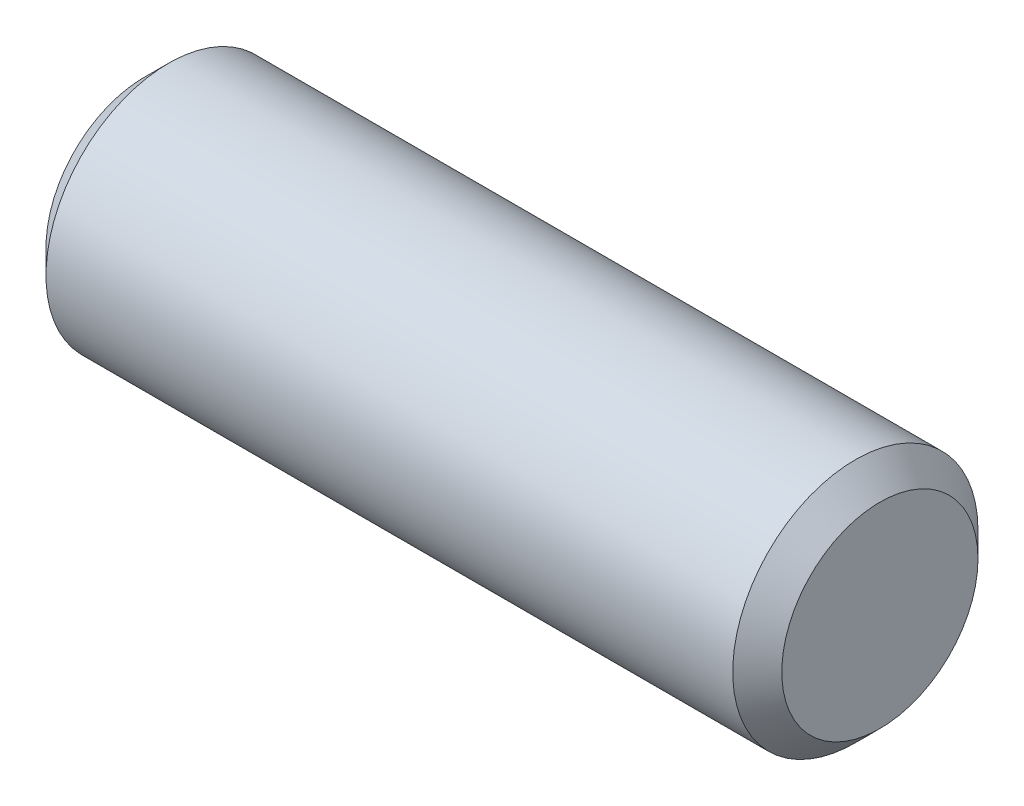
SolidWorks part; units mm, degrees
ref_plane "Front" through (0, 0, 0) normal (0, 0, 1) x (1, 0, 0)
ref_plane "Top" through (0, 0, 0) normal (0, 1, 0) x (1, 0, 0)
ref_plane "Right" through (0, 0, 0) normal (1, 0, 0) x (0, 0, -1)
sketch "Sketch1" plane through (0, 0, 0) normal (0, 0, 1) x (1, 0, 0)
  line L0 (-1.1906, 0) -> (1.1906, 0) construction
  line L1 (1.1906, 0.3969) -> (1.1906, -0.3969) construction
  line L2 (-1.1906, 0.3969) -> (-1.1906, -0.3969) construction
sketch "Sketch2" plane through (0, 0, 0) normal (1, 0, 0) x (0, 0, -1)
  line L0 (0.3969, 0) -> (-0.3969, 0) construction
  circle A0 centre (0, 0) radius 0.3969
  point P6 (0, 0)
  dimension "D1" = 0.7937
extrude "Extrude1" add sketch "Sketch2" against normal up to vertex (1.1906 mm away) and the other way up to vertex (1.1906 mm away) up to point (-1.1906, 0.3969, 0) other way up to point (1.1906, 0.3969, 0)
chamfer "Chamfer1" distance 0.0794 angle 45 2 edges at (1.1906, 0, -0.3969) (-1.1906, 0, -0.3969)
ref_axis "Center Axis1" through (-12.2237, 0, 0) along (1, 0, 0)
ref_plane "Contact Plane1" through (-1.1906, 0, 0) normal (1, 0, 0) x (0, 0, -1)
ref_plane "Contact Plane2" through (1.1906, 0, 0) normal (1, 0, 0) x (0, 0, -1)
sketch "Sketch3" plane through (0, 0, 0) normal (0, 1, 0) x (1, 0, 0)
  line L0 (0, 0.3969) -> (0, -0.3969)
  line L1 (-1.1113, -0.3969) -> (1.1113, -0.3969) construction
  line L3 (1.1113, 0.3969) -> (-1.1113, 0.3969) construction
  line L4 (0.5, 0.3969) -> (0.5, -0.3969) construction
  point P3 (0, 0.3969)
  point P9 (0, -0.3969)
  dimension "D1" = 0.5
equation "\"D1@Chamfer1\" = \"Diameter@Sketch1\"*.1"
equation "\"D1@Sketch2\"=\"Diameter@Sketch1\""
